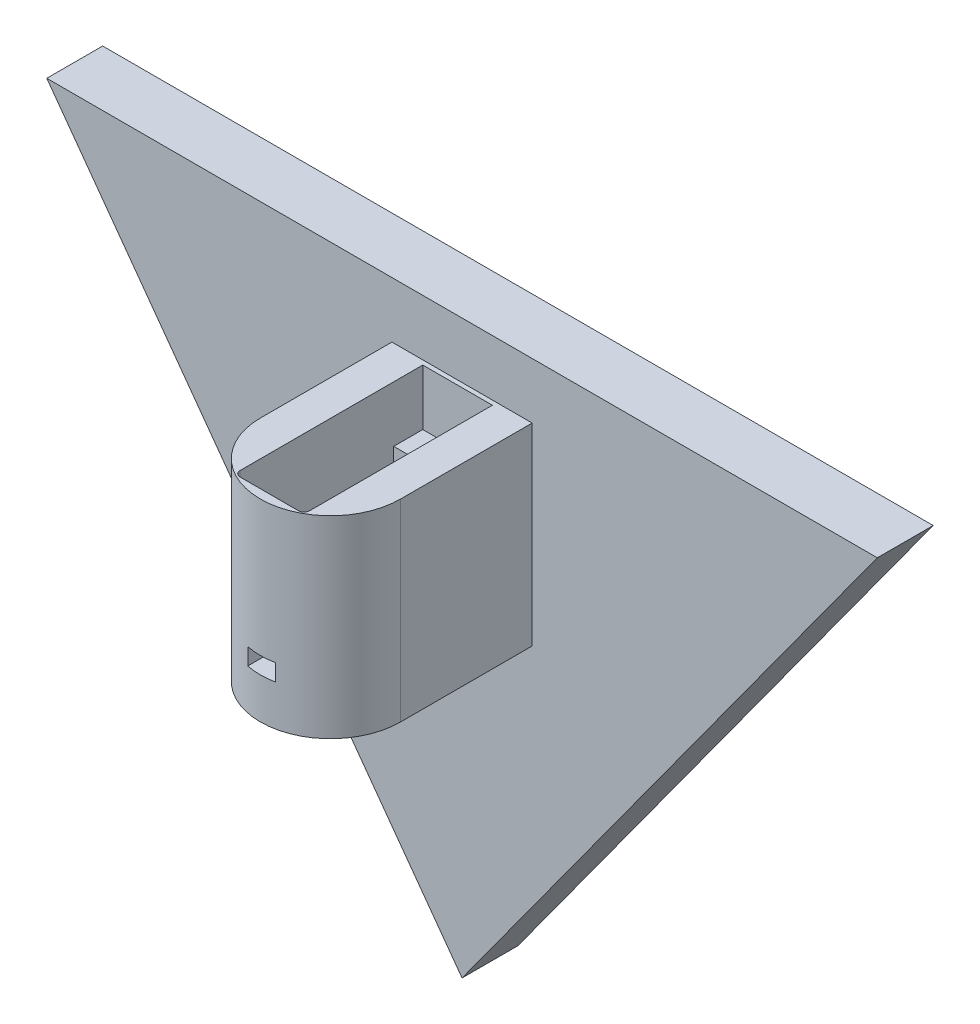
SolidWorks part; units mm, degrees
ref_plane "Front Plane" through (0, 0, 0) normal (0, 0, 1) x (1, 0, 0)
ref_plane "Top Plane" through (0, 0, 0) normal (0, 1, 0) x (1, 0, 0)
ref_plane "Right Plane" through (0, 0, 0) normal (1, 0, 0) x (0, 0, -1)
sketch "Sketch4" plane through (0, 0, 0) normal (0, 0, 1) x (1, 0, 0)
  line L0 (55, 0) -> (-55, 0) construction
  line L1 (-6.23, -9.975) -> (6.23, -9.975)
  line L2 (-6.23, -9.975) -> (-6.23, 7.275)
  line L3 (-6.23, 7.275) -> (6.23, 7.275)
  line L4 (6.23, -9.975) -> (6.23, 7.275)
  point P4 (0, 7.275)
  dimension "D1" = 12.46
  dimension "D2" = 17.25
  dimension "D3" = 9.975
extrude "Boss-Extrude3" add sketch "Sketch4" along normal blind 6
sketch "Sketch8" plane through (0, -9.975, 0) normal (0, -1, 0) x (-1, 0, 0)
  circle A0 centre (0, -23.55) radius 12.5468
  circle A1 centre (0, -23.55) radius 11.15
  dimension "D1" = 22.3
  dimension "D2" = 23.55
extrude "Boss-Extrude6" add sketch "Sketch8" along normal blind 7.3 and the other way up to surface (17.25 mm away) other way up to face at (0, 7.275, 3)
sketch "Sketch5" plane through (0, 7.275, 0) normal (0, 1, 0) x (1, 0, 0)
  line L8 (12.5468, -23.55) -> (12.5468, 0)
  line L9 (12.5468, 0) -> (6.23, 0)
  line L10 (-12.5468, -23.55) -> (-12.5468, 0)
  line L11 (-12.5468, 0) -> (-6.23, 0)
  line L12 (-6.23, 0) -> (-6.23, -29.7)
  line L14 (6.23, -29.7) -> (6.23, 0)
  line L15 (-6.23, -29.7) -> (6.23, -29.7)
  line L16 (6.23, -6) -> (-6.23, -6) construction
  circle A0 centre (0, -23.55) radius 12.5468 construction
  arc A1 (-12.5468, -23.55) -> (12.5468, -23.55) centre (0, -23.55) ccw
  dimension "D1" = 23.7
  dimension "D2" = 23.55
extrude "Boss-Extrude4" add sketch "Sketch5" against normal up to surface (17.25 mm away) up to face at (0, -9.975, 3)
sketch "Sketch6" plane through (0, 7.275, 0) normal (0, 1, 0) x (1, 0, 0)
  line L0 (6.23, -6) -> (-6.23, -6) construction
  line L3 (6.23, -29.7) -> (-6.23, -29.7) construction
  circle A0 centre (0, -3.5) radius 2
  circle A1 centre (0, -32.2) radius 2
  dimension "D1" = 4
  dimension "D3" = 4
  dimension "D2" = 2.5
  dimension "D4" = 2.5
extrude "Cut-Extrude1" cut sketch "Sketch6" against normal blind 5
chamfer "Chamfer1" distance 0.5 angle 60 2 edges at (0, 7.275, 5.5) (0, 7.275, 34.2) first distance on face at (0, 7.275, 5.5)
sketch "Sketch10" plane through (0, 7.275, 0) normal (0, 1, 0) x (1, 0, 0)
  line L1 (-6.23, -6) -> (6.23, -6)
  line L2 (-6.23, -6) -> (-6.23, -29.7)
  line L3 (-6.23, -29.7) -> (6.23, -29.7)
  line L4 (6.23, -6) -> (6.23, -29.7)
extrude "Cut-Extrude3" cut sketch "Sketch10" against normal up to surface (17.25 mm away) up to face at (0, -9.975, 27.1007)
ref_plane "Plane1" through (0, 0, 36.0968) normal (0, 0, 1) x (1, 0, 0)
sketch "Sketch11" plane through (0, 0, 36.0968) normal (0, 0, 1) x (1, 0, 0)
  line L0 (-11.15, -9.975) -> (11.15, -9.975) construction
  line L1 (-2.5, -6.975) -> (2.5, -6.975)
  line L2 (-2.5, -6.975) -> (-2.5, -9.975)
  line L3 (-2.5, -9.975) -> (2.5, -9.975)
  line L4 (2.5, -6.975) -> (2.5, -9.975)
  point P4 (0, -6.975)
  dimension "D1" = 0
  dimension "D2" = 5
  dimension "D3" = 3
extrude "Cut-Extrude4" cut sketch "Sketch11" against normal up to next
sketch "Sketch13" plane through (0, -17.275, 0) normal (0, -1, 0) x (1, 0, 0)
  line L0 (-12.5468, 23.55) -> (-12.5468, 0)
  line L1 (-12.5468, 0) -> (12.5468, 0)
  line L2 (12.5468, 0) -> (12.5468, 23.55)
  arc A0 (-12.5468, 23.55) -> (12.5468, 23.55) centre (0, 23.55) ccw
  point P3 (0, 0)
extrude "Boss-Extrude7" add sketch "Sketch13" against normal up to surface (7.3 mm away) up to face at (6.0145, -9.975, 27.3356)
sketch "Sketch15" plane through (0, 7.275, 0) normal (0, 1, 0) x (1, 0, 0)
  line L0 (-12.5468, 0) -> (12.5468, 0)
  line L1 (12.5468, 0) -> (12.5468, -23.55)
  line L2 (-12.5468, 0) -> (-12.5468, -23.55)
  line L3 (6.23, -6) -> (6.23, -29.7) construction
  line L4 (-6.23, -0.8) -> (6.23, -0.8)
  line L5 (-6.23, -0.8) -> (-6.23, -33.5)
  line L6 (-5.23, -34.5) -> (5.23, -34.5)
  line L7 (6.23, -0.8) -> (6.23, -33.5)
  arc A0 (-12.5468, -23.55) -> (12.5468, -23.55) centre (0, -23.55) ccw
  circle A1 centre (0, -3.5) radius 2 construction
  arc A2 (5.23, -34.5) -> (6.23, -33.5) centre (5.23, -33.5) ccw
  arc A3 (-6.23, -33.5) -> (-5.23, -34.5) centre (-5.23, -33.5) ccw
  point P15 (0, -0.8)
  dimension "D1" = 0.8
  dimension "D3" = 1
  dimension "D2" = 2.7
  dimension "D4" = 0
  dimension "D5" = 34.5
extrude "Boss-Extrude9" add sketch "Sketch15" along normal blind 10
sketch "Sketch1" plane through (0, 0, 0) normal (0, 0, 1) x (1, 0, 0)
  line L0 (0, -75) -> (74.3071, 27.275)
  line L1 (74.3071, 27.275) -> (-74.3071, 27.275)
  line L2 (-74.3071, 27.275) -> (0, -75)
  line L3 (6.23, 17.275) -> (-6.23, 17.275) construction
  line L4 (13.8015, 0) -> (-13.8015, 0) construction
  point P10 (0, 27.275)
  dimension "D2" = 10
  dimension "D1" = 72
  dimension "D3" = 75
extrude "Offset R" add sketch "Sketch1" against normal blind 10 contours L2 L0 L1
sketch "Sketch16" plane through (0, -17.275, 0) normal (0, -1, 0) x (1, 0, 0)
  circle A0 centre (0, 23.55) radius 11.15
  circle A1 centre (0, 23.55) radius 7.15
  circle A2 centre (0, 23.55) radius 11.15 construction
  dimension "D1" = 14.3
extrude "Boss-Extrude10" add sketch "Sketch16" against normal up to surface (7.3 mm away) up to face at (6.0145, -9.975, 27.3356)
sketch "Sketch17" plane through (0, -17.275, 0) normal (0, -1, 0) x (1, 0, 0)
  circle A0 centre (0, 23.55) radius 10.15
  circle A1 centre (0, 23.55) radius 7.15
  circle A2 centre (0, 23.55) radius 7.15 construction
  dimension "D1" = 20.3
extrude "Cut-Extrude5" cut sketch "Sketch17" against normal blind 1.3
